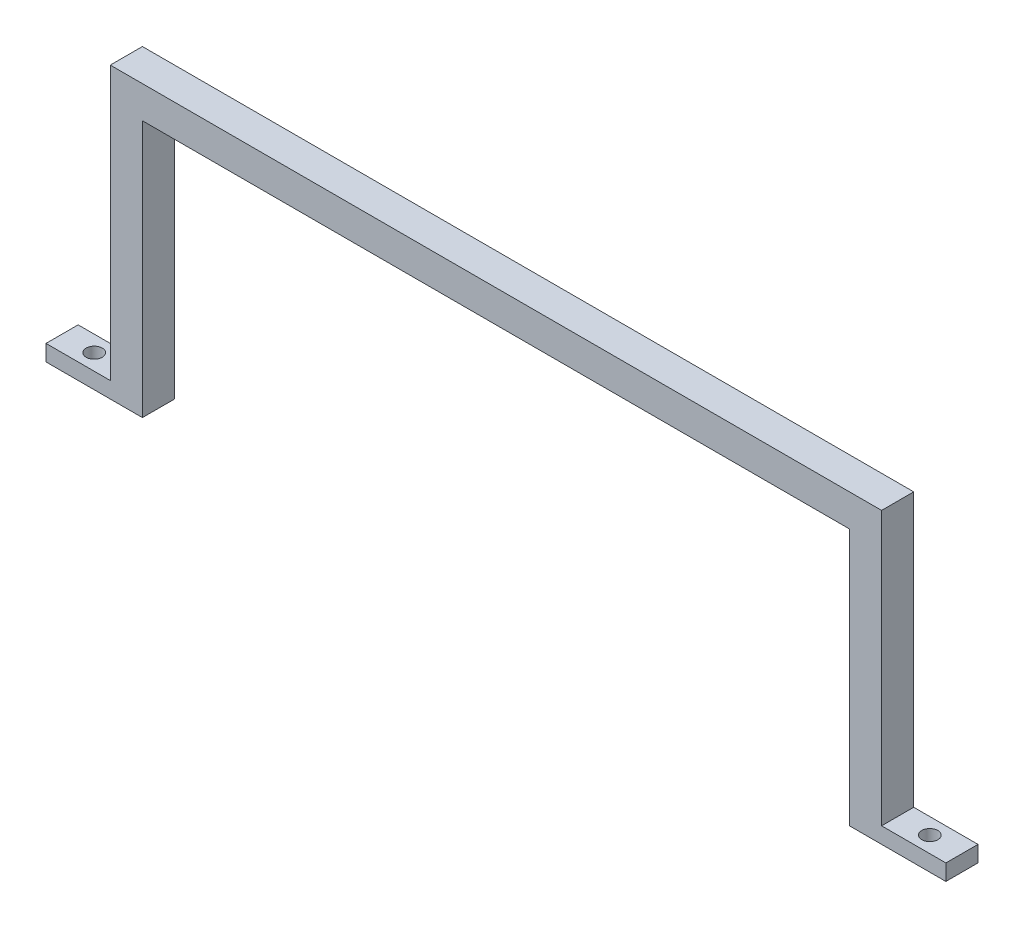
SolidWorks part; units mm, degrees
ref_plane "Front Plane" through (0, 0, 0) normal (0, 0, 1) x (1, 0, 0)
ref_plane "Top Plane" through (0, 0, 0) normal (0, 1, 0) x (1, 0, 0)
ref_plane "Right Plane" through (0, 0, 0) normal (1, 0, 0) x (0, 0, -1)
sketch "Sketch1" plane through (0, 0, 0) normal (0, 1, 0) x (1, 0, 0)
  line L1 (-76.2, 3.175) -> (76.2, 3.175)
  line L2 (-76.2, 3.175) -> (-76.2, -3.175)
  line L3 (-76.2, -3.175) -> (76.2, -3.175)
  line L4 (76.2, 3.175) -> (76.2, -3.175)
  line L5 (-76.2, 3.175) -> (76.2, -3.175) construction
  line L6 (-76.2, -3.175) -> (76.2, 3.175) construction
  point P0 (0, 0)
  dimension "D1" = 6.35
  dimension "D2" = 152.4
extrude "Boss-Extrude1" add sketch "Sketch1" along normal blind 6.35
sketch "Sketch2" plane through (0, 0, 0) normal (0, -1, 0) x (1, 0, 0)
  line L0 (76.2, -3.175) -> (-76.2, -3.175) construction
  line L1 (-76.2, 3.175) -> (-69.85, 3.175)
  line L2 (-76.2, 3.175) -> (-76.2, -3.175)
  line L3 (-76.2, -3.175) -> (-69.85, -3.175)
  line L4 (-69.85, 3.175) -> (-69.85, -3.175)
  dimension "D1" = 6.35
extrude "Boss-Extrude2" add sketch "Sketch2" along normal blind 50.8
sketch "Sketch3" plane through (-76.2, 0, 0) normal (-1, 0, 0) x (0, 0, 1)
  line L0 (3.175, 6.35) -> (3.175, -50.8) construction
  line L1 (-3.175, -50.8) -> (3.175, -50.8)
  line L2 (-3.175, -50.8) -> (-3.175, -47.625)
  line L3 (-3.175, -47.625) -> (3.175, -47.625)
  line L4 (3.175, -50.8) -> (3.175, -47.625)
  dimension "D1" = 3.175
extrude "Boss-Extrude3" add sketch "Sketch3" along normal blind 12.7
mirror "Mirror1" about plane through (0, 0, 0) normal (1, 0, 0) of "Boss-Extrude3", "Boss-Extrude2"
sketch "Sketch4" plane through (0, -47.625, 0) normal (0, 1, 0) x (1, 0, 0)
  line L0 (-88.9, 3.175) -> (-76.2, 3.175) construction
  line L1 (-88.9, -3.175) -> (-88.9, 3.175) construction
  circle A0 centre (-82.55, 0) radius 1.5875
  dimension "D1" = 3.175
  dimension "D3" = 6.35
  dimension "D2" = 3.175
extrude "Cut-Extrude1" cut sketch "Sketch4" against normal up to next
mirror "Mirror2" about plane through (0, 0, 0) normal (1, 0, 0) of "Cut-Extrude1"
